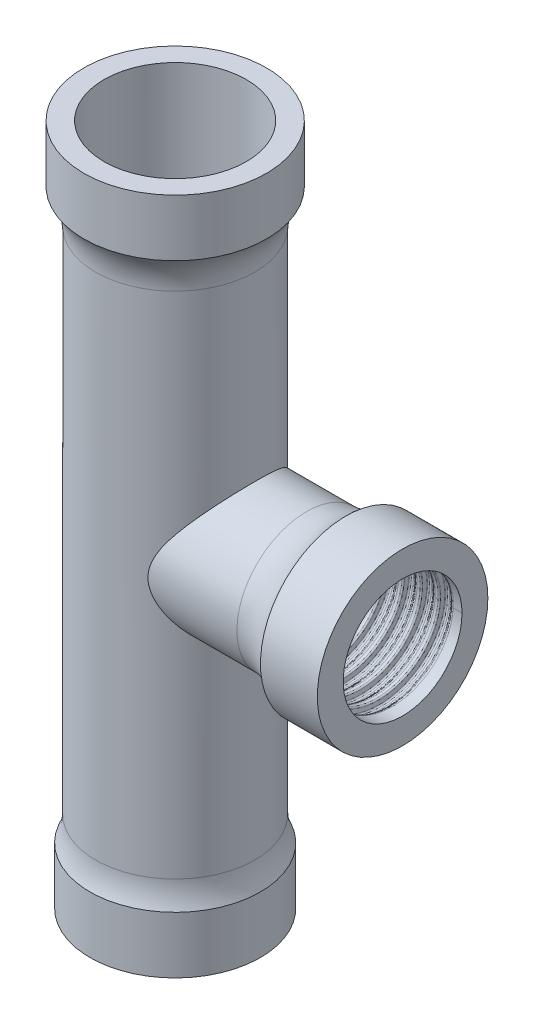
SolidWorks part; units mm, degrees
ref_plane "前基準面" through (0, 0, 0) normal (0, 0, 1) x (1, 0, 0)
ref_plane "上基準面" through (0, 0, 0) normal (0, 1, 0) x (1, 0, 0)
ref_plane "右基準面" through (0, 0, 0) normal (1, 0, 0) x (0, 0, -1)
sketch "草圖1" plane through (0, 0, 0) normal (0, 1, 0) x (1, 0, 0)
  circle A0 centre (0, 0) radius 14
extrude "填料-伸長1" add sketch "草圖1" along normal blind 100
sketch "草圖2" plane through (0, 0, 0) normal (1, 0, 0) x (0, 0, -1)
  circle A0 centre (0, 50) radius 12
extrude "填料-伸長2" add sketch "草圖2" along normal blind 30
sketch "草圖3" plane through (30, 0, 0) normal (1, 0, 0) x (0, 0, -1)
  circle A0 centre (0, 49.7593) radius 10.4516
extrude "除料-伸長1" cut sketch "草圖3" against normal blind 30
sketch "草圖4" plane through (0, 0, 0) normal (0, -1, 0) x (-1, 0, 0)
  circle A0 centre (0, 0) radius 12.5145
extrude "除料-伸長2" cut sketch "草圖4" against normal blind 100
sketch "草圖5" plane through (0, 0, 0) normal (0, -1, 0) x (1, 0, 0)
  circle A0 centre (0, 0) radius 15
  circle A1 centre (0, 0) radius 12.5145 construction
  circle A2 centre (0, 0) radius 12.5145
extrude "填料-伸長3" add sketch "草圖5" along normal blind 10
sketch "草圖6" plane through (0, 100, 0) normal (0, 1, 0) x (1, 0, 0)
  circle A0 centre (0, 0) radius 16.0687
  circle A1 centre (0, 0) radius 12.5145 construction
  circle A2 centre (0, 0) radius 12.5145
extrude "填料-伸長4" add sketch "草圖6" along normal blind 10
sketch "草圖7" plane through (30, 0, 0) normal (1, 0, 0) x (0, 0, -1)
  circle A0 centre (0, 49.7593) radius 15
  circle A1 centre (0, 49.7593) radius 10.4516 construction
  circle A2 centre (0, 49.7593) radius 10.4516
extrude "填料-伸長5" add sketch "草圖7" along normal blind 10
fillet "圓角2" radius 10 1 edges at (30, 50, -12)
fillet "圓角3" radius 10 1 edges at (0, 0, 14)
fillet "圓角4" radius 10 1 edges at (0, 100, 14)
thread "螺紋1" pitch 3.175 method cut profile "螺紋輪廓1" start angle 4, offset 0, length 0, pitch 3.175, diameter 20.9032
ref_plane "平面1" through (40, 50.4884, 10.4262) normal (0, -0.9976, 0.0698) x (0, 0.0698, 0.9976)
sketch "螺紋輪廓1" plane through (40, 50.4884, 10.4262) normal (0, -0.9976, 0.0698) x (0, 0.0698, 0.9976)
  line L0 (0, 0) -> (0, 3.175) construction
  line L1 (0, 0) -> (0, 2.6624)
  line L2 (0.254, 2.6624) -> (1.0668, 2.6624) construction
  line L3 (1.0668, 2.048) -> (1.0668, 1.6981)
  line L4 (0.8569, 2.2981) -> (0.2099, 2.4122)
  line L5 (0.8436, 1.1592) -> (0.2232, 0.5388)
  line L6 (0.762, 0) -> (1.0668, 0) construction
  arc A0 (0.2099, 2.4122) -> (0, 2.6624) centre (0.254, 2.6624) cw
  arc A1 (0.2232, 0.5388) -> (0, 0) centre (0.762, 0) ccw
  arc A2 (1.0668, 1.6981) -> (0.8436, 1.1592) centre (0.3048, 1.6981) cw
  arc A3 (1.0668, 2.048) -> (0.8569, 2.2981) centre (0.8128, 2.048) ccw
  point P10 (1.0668, 2.2611)
  point P17 (1.0668, 1.3824)
  point P18 (0, 2.4492)
  point P19 (0, 0.3156)
  point P20 (0, 0)
  dimension "RootFillet1" = 0.254
  dimension "RootFillet2" = 0.762
  dimension "CrestFillet2" = 0.762
  dimension "CrestFillet1" = 0.254
  dimension "Pitch" = 3.175
  dimension "Angle1" = 10
  dimension "Angle2" = 45
  dimension "a" = 2.1336
  dimension "b" = 1.0668
  dimension "c" = 0.8787
